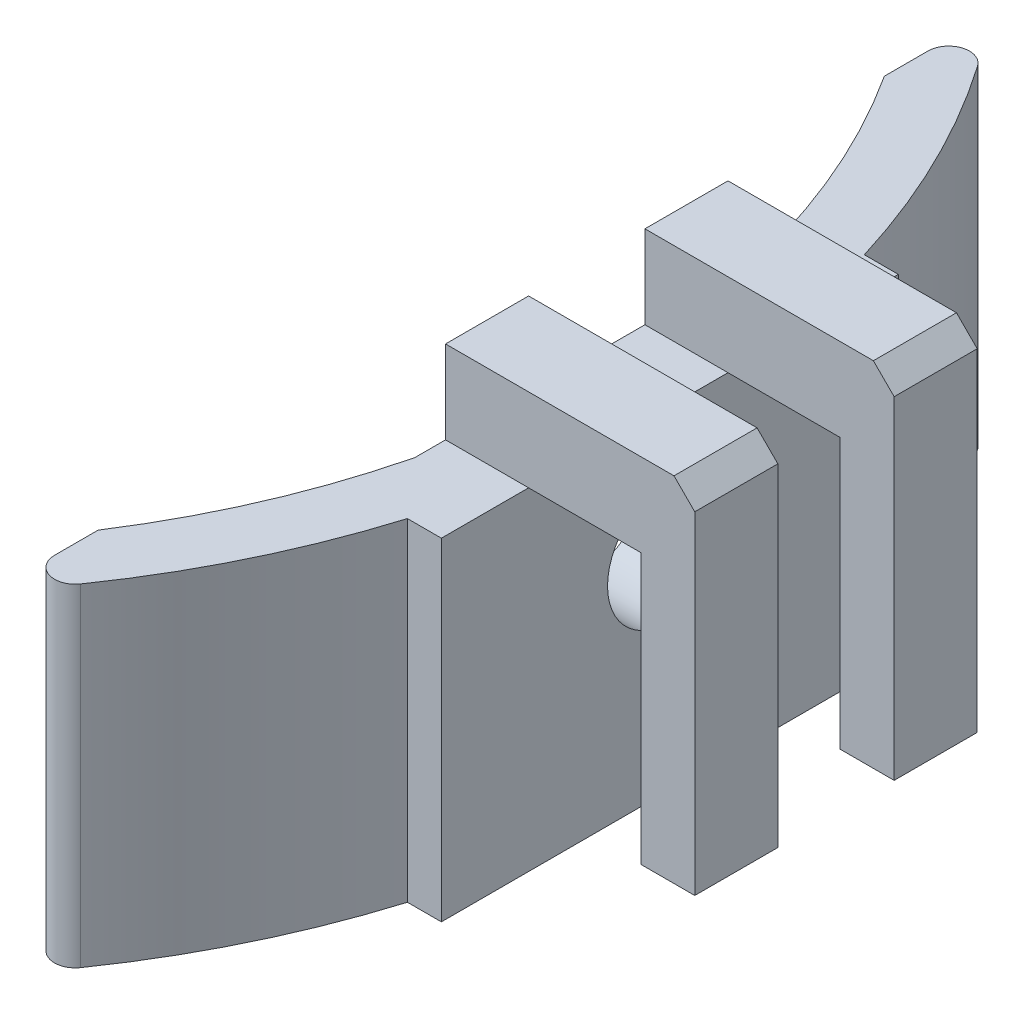
SolidWorks part; units mm, degrees
ref_plane "前视基准面" through (0, 0, 0) normal (0, 0, 1) x (1, 0, 0)
ref_plane "上视基准面" through (0, 0, 0) normal (0, 1, 0) x (1, 0, 0)
ref_plane "右视基准面" through (0, 0, 0) normal (1, 0, 0) x (0, 0, -1)
other "Configuration Table"
sketch "草图1" plane through (0, 0, 0) normal (1, 0, 0) x (0, 0, -1)
  line L0 (0, 3) -> (0, 11.0564) construction
  line L1 (-5.5, -3) -> (5.5, -3)
  line L2 (-5.5, -3) -> (-5.5, 3)
  line L3 (-5.5, 3) -> (-3.4, 3)
  line L4 (5.5, -3) -> (5.5, 3)
  line L5 (-5.5, -3) -> (0, 0) construction
  line L6 (-5.5, 3) -> (5.5, -3) construction
  line L7 (-1.4, 3) -> (1.4, 3)
  line L9 (-1.4, 3) -> (-1.4, 5)
  line L10 (-1.4, 5) -> (-3.4, 5)
  line L11 (-3.4, 3) -> (-3.4, 5)
  line L13 (1.4, 3) -> (1.4, 5)
  line L14 (1.4, 5) -> (3.4, 5)
  line L15 (3.4, 3) -> (3.4, 5)
  line L16 (3.4, 3) -> (5.5, 3)
  point P0 (0, 0)
  dimension "D1" = 11
  dimension "D2" = 6
  dimension "D3" = 2.8
  dimension "D4" = 1.4
  dimension "D5" = 2
  dimension "D6" = 2
  dimension "D7" = 2
  dimension "D8" = 2
  dimension "D9" = 5.5
extrude "凸台-拉伸1" add sketch "草图1" along normal blind 2
sketch "草图2" plane through (0, -3, 0) normal (0, -1, 0) x (1, 0, 0)
  line L3 (-2.3, 10.5125) -> (-2.3, 9.464)
  line L4 (0, 5.5) -> (0, -5.5) construction
  line L8 (-2.3, -9.464) -> (-2.3, -10.5125)
  arc A2 (-1.3897, 10.7982) -> (-1.3897, -10.7982) centre (-16.8942, 0) cw
  arc A3 (-2.3, 9.464) -> (-2.3, -9.464) centre (-16.8942, 0) cw
  arc A4 (-3.4586, 11.0473) -> (-3.4586, -11.0473) centre (-16.8942, 0) cw construction
  arc A5 (-2.3, 12) -> (-2.3, -12) centre (-16.8942, 0) cw construction
  arc A6 (-1.3897, -10.7982) -> (-2.3, -10.5125) centre (-1.8, -10.5125) cw
  arc A7 (-1.3897, 10.7982) -> (-2.3, 10.5125) centre (-1.8, 10.5125) ccw
  dimension "D4" = 1.5
  dimension "D2" = 0.5
  dimension "D1" = 2.3
sketch "草图3" plane through (2, 0, 0) normal (1, 0, 0) x (0, 0, -1)
  line L0 (-3.4, 3) -> (-1.4, 3)
  line L1 (1.4, 3) -> (3.4, 3)
  line L12 (-5.5, -3) -> (5.5, -3)
  line L13 (5.5, -3) -> (5.5, 3)
  line L14 (5.5, 3) -> (3.4, 3)
  line L15 (3.4, 3) -> (3.4, 5)
  line L16 (3.4, 5) -> (1.4, 5)
  line L17 (1.4, 5) -> (1.4, 3)
  line L18 (1.4, 3) -> (-1.4, 3)
  line L19 (-1.4, 3) -> (-1.4, 5)
  line L20 (-1.4, 5) -> (-3.4, 5)
  line L21 (-3.4, 5) -> (-3.4, 3)
  line L22 (-3.4, 3) -> (-5.5, 3)
  line L23 (-5.5, 3) -> (-5.5, -3)
  line L27 (3.4, 3) -> (3.4, 5)
  line L28 (3.4, 5) -> (1.4, 5)
  line L29 (1.4, 5) -> (1.4, 3)
  line L31 (-1.4, 3) -> (-1.4, 5)
  line L32 (-1.4, 5) -> (-3.4, 5)
  line L33 (-3.4, 5) -> (-3.4, 3)
  dimension "D1" = 0
extrude "凸台-拉伸3" add sketch "草图3" along normal blind 4
sketch "草图4" plane through (0, 3, 0) normal (0, -1, 0) x (1, 0, 0)
  line L0 (6, -3.4) -> (2, -3.4) construction
  line L1 (6, 3.4) -> (4.7, 3.4)
  line L2 (6, 3.4) -> (6, 1.4)
  line L3 (6, -3.4) -> (4.7, -3.4)
  line L4 (4.7, 3.4) -> (4.7, 1.4)
  line L5 (6, -1.4) -> (2, -1.4) construction
  line L6 (6, 1.4) -> (2, 1.4) construction
  line L7 (6, -1.4) -> (4.7, -1.4)
  line L8 (6, 1.4) -> (4.7, 1.4)
  line L9 (4.7, -1.4) -> (4.7, -3.4)
  line L10 (6, -1.4) -> (6, -3.4)
  dimension "D1" = 1.3
extrude "凸台-拉伸4" add sketch "草图4" along normal blind 6.5
sketch "草图5" plane through (0, -3, 0) normal (0, -1, 0) x (1, 0, 0)
  line L6 (2, 5.5) -> (0, 5.5)
  line L8 (0, 5.5) -> (0, -5.5)
  line L10 (0, -5.5) -> (2, -5.5)
  line L11 (2, -5.5) -> (2, 5.5)
  line L12 (2, 5.5) -> (0, 5.5)
  line L14 (0, 5.5) -> (0, -5.5)
  line L16 (0, -5.5) -> (2, -5.5)
  line L17 (2, -5.5) -> (2, 5.5)
  dimension "D1" = 0
extrude "凸台-拉伸5" add sketch "草图5" along normal blind 2
chamfer "倒角1" distance 0.5 angle 45 2 edges at (6, 5, 2.4) (6, 5, -2.4)
sketch "草图6" plane through (0, 0, 0) normal (-1, 0, 0) x (0, 0, 1)
  circle A0 centre (0, 0) radius 1.5
extrude "切除-拉伸1" cut sketch "草图6" against normal blind 2
extrude "凸台-拉伸6" add sketch "草图2" along normal blind 2 and the other way blind 6 contours A3 L8 A6 A2 A7 L3
sketch "草图7" plane through (2, 0, 0) normal (1, 0, 0) x (0, 0, -1)
  arc A0 (0, -1.5) -> (0, 1.5) centre (0, 0) ccw construction
  arc A1 (0, 1.5) -> (0, -1.5) centre (0, 0) ccw construction
  arc A2 (0, -1.5) -> (0, 1.5) centre (0, 0) ccw
  arc A3 (0, 1.5) -> (0, -1.5) centre (0, 0) ccw
extrude "切除-拉伸2" cut sketch "草图7" against normal blind 2
